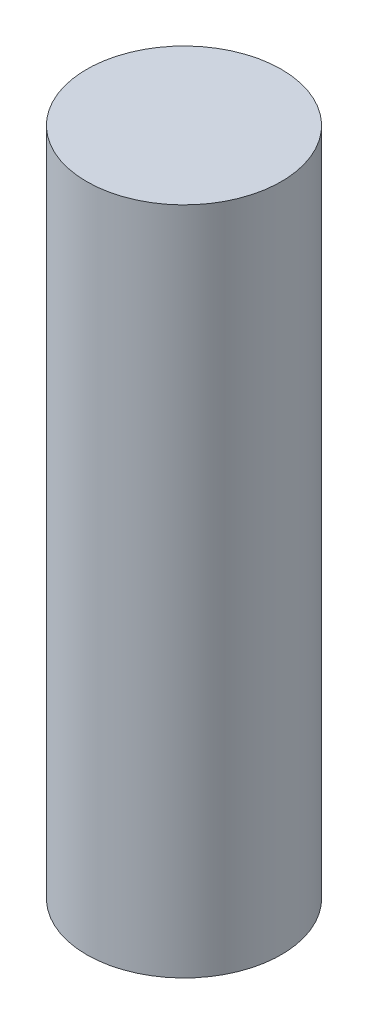
SolidWorks part; units mm, degrees
material "6061-T4 (SS)"
ref_plane "Front Plane" through (0, 0, 0) normal (0, 0, 1) x (1, 0, 0)
ref_plane "Top Plane" through (0, 0, 0) normal (0, 1, 0) x (1, 0, 0)
ref_plane "Right Plane" through (0, 0, 0) normal (1, 0, 0) x (0, 0, -1)
sketch "Sketch1" plane through (0, 0, 0) normal (0, 1, 0) x (1, 0, 0)
  circle A0 centre (0, 0) radius 12.5
  dimension "D1" = 25
extrude "Boss-Extrude1" add sketch "Sketch1" along normal blind 86
